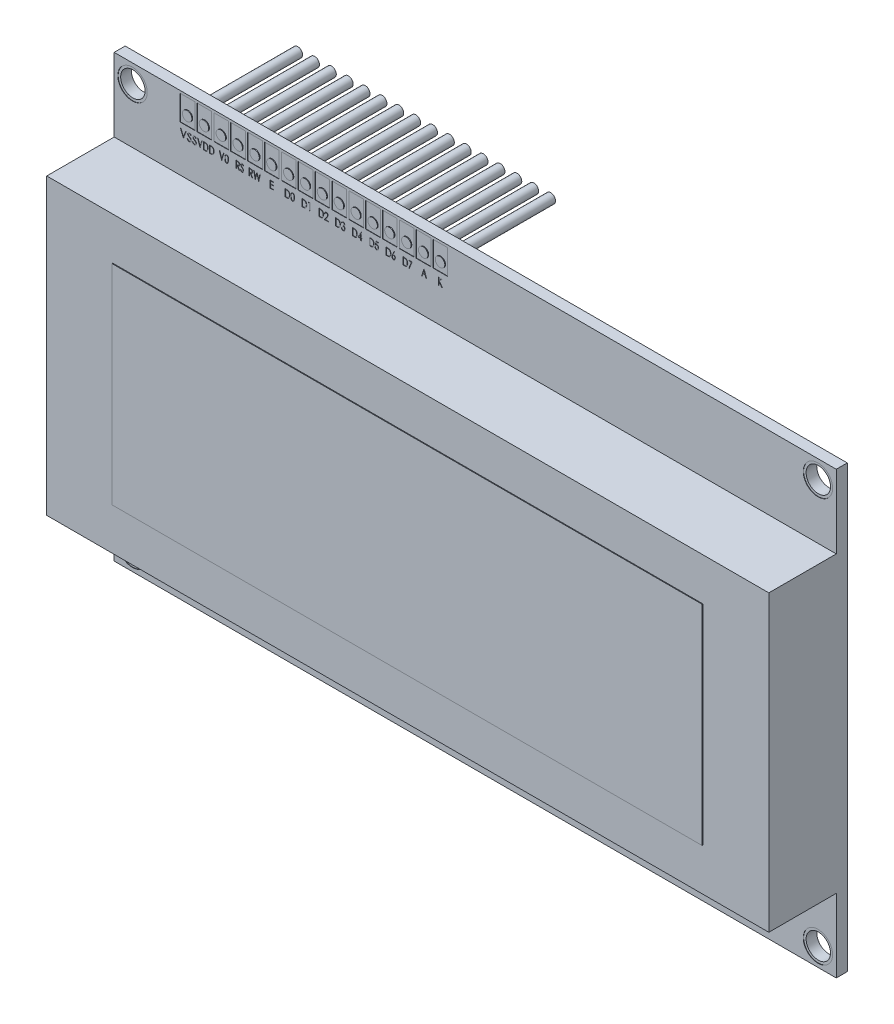
SolidWorks part; units mm, degrees
ref_plane "Front Plane" through (0, 0, 0) normal (0, 0, 1) x (1, 0, 0)
ref_plane "Top Plane" through (0, 0, 0) normal (0, 1, 0) x (1, 0, 0)
ref_plane "Right Plane" through (0, 0, 0) normal (1, 0, 0) x (0, 0, -1)
sketch "Sketch1" plane through (0, 0, 0) normal (0, 0, 1) x (1, 0, 0)
  line L0 (0, 40.8512) -> (0, -48.0365) construction
  line L1 (49.25, -30.05) -> (-49.25, -30.05)
  line L2 (49.25, -30.05) -> (49.25, 30.05)
  line L3 (49.25, 30.05) -> (-49.25, 30.05)
  line L4 (-49.25, -30.05) -> (-49.25, 30.05)
  line L5 (49.25, -30.05) -> (-49.25, 30.05) construction
  line L6 (49.25, 30.05) -> (-49.25, -30.05) construction
  line L7 (-58.2061, 0) -> (68.8537, 0) construction
  circle A0 centre (-46.75, 27.55) radius 1.665
  circle A1 centre (46.75, 27.55) radius 1.665
  circle A2 centre (-46.75, -27.55) radius 1.665
  circle A3 centre (46.75, -27.55) radius 1.665
  circle A4 centre (-39.25, 27.55) radius 0.65
  circle A5 centre (-36.95, 27.55) radius 0.65
  circle A6 centre (-34.65, 27.55) radius 0.65
  circle A7 centre (-32.35, 27.55) radius 0.65
  circle A8 centre (-30.05, 27.55) radius 0.65
  circle A9 centre (-27.75, 27.55) radius 0.65
  circle A10 centre (-25.45, 27.55) radius 0.65
  circle A11 centre (-23.15, 27.55) radius 0.65
  circle A12 centre (-20.85, 27.55) radius 0.65
  circle A13 centre (-18.55, 27.55) radius 0.65
  circle A14 centre (-16.25, 27.55) radius 0.65
  circle A15 centre (-13.95, 27.55) radius 0.65
  circle A16 centre (-11.65, 27.55) radius 0.65
  circle A17 centre (-9.35, 27.55) radius 0.65
  circle A18 centre (-7.05, 27.55) radius 0.65
  circle A19 centre (-4.75, 27.55) radius 0.65
  point P0 (0, 0)
  dimension "D5" = 3.33
  dimension "D6" = 1.3
  dimension "D1" = 98.5
  dimension "D2" = 60.1
  dimension "D3" = 2.5
  dimension "D4" = 2.5
  dimension "D7" = 2.5
  dimension "D8" = 10
  dimension "D9" = 16
extrude "Boss-Extrude1" add sketch "Sketch1" along normal mid plane 1.5
sketch "Sketch2" plane through (0, 0, 0.75) normal (0, 0, 1) x (1, 0, 0)
  line L0 (-49.25, 30.05) -> (-49.25, -30.05) construction
  line L1 (49.25, -20.05) -> (-49.25, -20.05)
  line L2 (49.25, -20.05) -> (49.25, 20.05)
  line L3 (49.25, 20.05) -> (-49.25, 20.05)
  line L4 (-49.25, -20.05) -> (-49.25, 20.05)
  line L5 (49.25, -20.05) -> (-49.25, 20.05) construction
  line L6 (49.25, 20.05) -> (-49.25, -20.05) construction
  line L7 (49.25, 30.05) -> (-49.25, 30.05) construction
  point P0 (0, 0)
  dimension "D1" = 10
  dimension "D2" = 40.1
  dimension "D3" = 98.5
extrude "Boss-Extrude2" add sketch "Sketch2" along normal blind 9.2
sketch "Sketch3" plane through (0, 0, 9.95) normal (0, 0, 1) x (1, 0, 0)
  line L0 (-49.25, 20.05) -> (-49.25, -20.05) construction
  line L1 (40.25, -14.25) -> (-40.25, -14.25)
  line L2 (40.25, -14.25) -> (40.25, 14.25)
  line L3 (40.25, 14.25) -> (-40.25, 14.25)
  line L4 (-40.25, -14.25) -> (-40.25, 14.25)
  line L5 (40.25, -14.25) -> (-40.25, 14.25) construction
  line L6 (40.25, 14.25) -> (-40.25, -14.25) construction
  line L7 (49.25, 20.05) -> (-49.25, 20.05) construction
  point P0 (0, 0)
  dimension "D1" = 9
  dimension "D2" = 5.8
extrude "Boss-Extrude3" add sketch "Sketch3" along normal blind 0.1
sketch "Sketch4" plane through (0, 0, 0.75) normal (0, 0, 1) x (1, 0, 0)
  line L0 (0, 45.5389) -> (0, -39.1221) construction
  line L1 (-62.9284, 0) -> (59.0171, 0) construction
  line L2 (-37.95, 29.7169) -> (-37.95, 26.3169)
  line L3 (-40.25, 29.7169) -> (-38.25, 29.7169)
  line L4 (-40.25, 29.7169) -> (-40.25, 26.3169)
  line L5 (-40.25, 26.3169) -> (-38.25, 26.3169)
  line L6 (-38.25, 29.7169) -> (-38.25, 26.3169)
  line L7 (-40.25, 29.7169) -> (-38.25, 26.3169) construction
  line L8 (-40.25, 26.3169) -> (-38.25, 29.7169) construction
  line L9 (-37.95, 29.7169) -> (-35.95, 29.7169)
  line L10 (-35.95, 29.7169) -> (-35.95, 26.3169)
  line L11 (-37.95, 26.3169) -> (-35.95, 26.3169)
  line L12 (-35.65, 29.7169) -> (-35.65, 26.3169)
  line L13 (-35.65, 29.7169) -> (-33.65, 29.7169)
  line L14 (-33.65, 29.7169) -> (-33.65, 26.3169)
  line L15 (-35.65, 26.3169) -> (-33.65, 26.3169)
  line L16 (-33.35, 29.7169) -> (-33.35, 26.3169)
  line L17 (-33.35, 29.7169) -> (-31.35, 29.7169)
  line L18 (-31.35, 29.7169) -> (-31.35, 26.3169)
  line L19 (-33.35, 26.3169) -> (-31.35, 26.3169)
  line L20 (-31.05, 29.7169) -> (-31.05, 26.3169)
  line L21 (-31.05, 29.7169) -> (-29.05, 29.7169)
  line L22 (-29.05, 29.7169) -> (-29.05, 26.3169)
  line L23 (-31.05, 26.3169) -> (-29.05, 26.3169)
  line L24 (-28.75, 29.7169) -> (-28.75, 26.3169)
  line L25 (-28.75, 29.7169) -> (-26.75, 29.7169)
  line L26 (-26.75, 29.7169) -> (-26.75, 26.3169)
  line L27 (-28.75, 26.3169) -> (-26.75, 26.3169)
  line L28 (-26.45, 29.7169) -> (-26.45, 26.3169)
  line L29 (-26.45, 29.7169) -> (-24.45, 29.7169)
  line L30 (-24.45, 29.7169) -> (-24.45, 26.3169)
  line L31 (-26.45, 26.3169) -> (-24.45, 26.3169)
  line L32 (-24.15, 29.7169) -> (-24.15, 26.3169)
  line L33 (-24.15, 29.7169) -> (-22.15, 29.7169)
  line L34 (-22.15, 29.7169) -> (-22.15, 26.3169)
  line L35 (-24.15, 26.3169) -> (-22.15, 26.3169)
  line L36 (-21.85, 29.7169) -> (-21.85, 26.3169)
  line L37 (-21.85, 29.7169) -> (-19.85, 29.7169)
  line L38 (-19.85, 29.7169) -> (-19.85, 26.3169)
  line L39 (-21.85, 26.3169) -> (-19.85, 26.3169)
  line L40 (-19.55, 29.7169) -> (-19.55, 26.3169)
  line L41 (-19.55, 29.7169) -> (-17.55, 29.7169)
  line L42 (-17.55, 29.7169) -> (-17.55, 26.3169)
  line L43 (-19.55, 26.3169) -> (-17.55, 26.3169)
  line L44 (-17.25, 29.7169) -> (-17.25, 26.3169)
  line L45 (-17.25, 29.7169) -> (-15.25, 29.7169)
  line L46 (-15.25, 29.7169) -> (-15.25, 26.3169)
  line L47 (-17.25, 26.3169) -> (-15.25, 26.3169)
  line L48 (-14.95, 29.7169) -> (-14.95, 26.3169)
  line L49 (-14.95, 29.7169) -> (-12.95, 29.7169)
  line L50 (-12.95, 29.7169) -> (-12.95, 26.3169)
  line L51 (-14.95, 26.3169) -> (-12.95, 26.3169)
  line L52 (-12.65, 29.7169) -> (-12.65, 26.3169)
  line L53 (-12.65, 29.7169) -> (-10.65, 29.7169)
  line L54 (-10.65, 29.7169) -> (-10.65, 26.3169)
  line L55 (-12.65, 26.3169) -> (-10.65, 26.3169)
  line L56 (-10.35, 29.7169) -> (-10.35, 26.3169)
  line L57 (-10.35, 29.7169) -> (-8.35, 29.7169)
  line L58 (-8.35, 29.7169) -> (-8.35, 26.3169)
  line L59 (-10.35, 26.3169) -> (-8.35, 26.3169)
  line L60 (-8.05, 29.7169) -> (-8.05, 26.3169)
  line L61 (-8.05, 29.7169) -> (-6.05, 29.7169)
  line L62 (-6.05, 29.7169) -> (-6.05, 26.3169)
  line L63 (-8.05, 26.3169) -> (-6.05, 26.3169)
  line L64 (-5.75, 29.7169) -> (-5.75, 26.3169)
  line L65 (-5.75, 29.7169) -> (-3.75, 29.7169)
  line L66 (-3.75, 29.7169) -> (-3.75, 26.3169)
  line L67 (-5.75, 26.3169) -> (-3.75, 26.3169)
  circle A0 centre (-46.75, 27.55) radius 2.0028
  circle A1 centre (46.75, 27.55) radius 2.0028
  circle A2 centre (46.75, -27.55) radius 2.0028
  circle A3 centre (-46.75, -27.55) radius 2.0028
  point P14 (-39.25, 28.0169)
  dimension "D1" = 2
  dimension "D2" = 3.4
  dimension "D3" = 16
extrude "Cut-Extrude1" cut sketch "Sketch4" against normal blind 0.05
sketch "Sketch5" plane through (0, 0, 0.75) normal (0, 0, 1) x (1, 0, 0)
  line L0 (-40.274, 24.6356) -> (2.9618, 24.6356) construction
  text T0 "VSS" font "Century Gothic" height 1
  text T1 "        VDD  V0   RS  RW    E     D0   D1   D2   D3   D4   D5   D6   D7    A     K" font "Century Gothic" height 1
extrude "Cut-Extrude2" cut sketch "Sketch5" against normal blind 0.05
sketch "Sketch7" plane through (0, 0, 0.7) normal (0, 0, 1) x (1, 0, 0)
  circle A0 centre (-4.75, 27.55) radius 0.65
  circle A1 centre (-7.05, 27.55) radius 0.65
  circle A2 centre (-9.35, 27.55) radius 0.65
  circle A3 centre (-11.65, 27.55) radius 0.65
  circle A4 centre (-13.95, 27.55) radius 0.65
  circle A5 centre (-16.25, 27.55) radius 0.65
  circle A6 centre (-18.55, 27.55) radius 0.65
  circle A7 centre (-20.85, 27.55) radius 0.65
  circle A8 centre (-23.15, 27.55) radius 0.65
  circle A9 centre (-25.45, 27.55) radius 0.65
  circle A10 centre (-27.75, 27.55) radius 0.65
  circle A11 centre (-30.05, 27.55) radius 0.65
  circle A12 centre (-32.35, 27.55) radius 0.65
  circle A13 centre (-34.65, 27.55) radius 0.65
  circle A14 centre (-36.95, 27.55) radius 0.65
  circle A15 centre (-39.25, 27.55) radius 0.65
  dimension "D1" = 16
extrude "Boss-Extrude4" add sketch "Sketch7" against normal blind 15 and the other way blind 0.1
